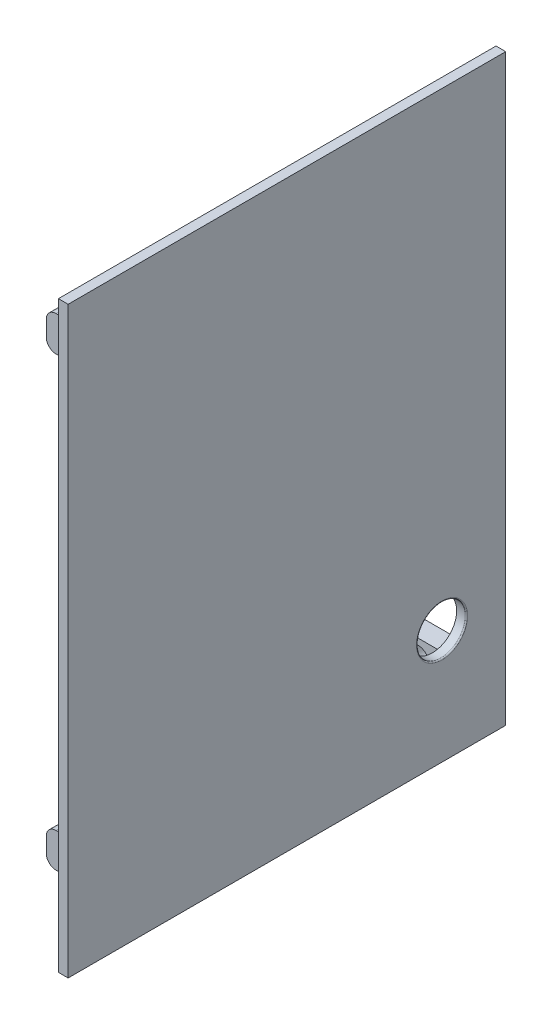
SolidWorks part; units mm, degrees
ref_plane "Front Plane" through (0, 0, 0) normal (0, 0, 1) x (1, 0, 0)
ref_plane "Top Plane" through (0, 0, 0) normal (0, 1, 0) x (1, 0, 0)
ref_plane "Right Plane" through (0, 0, 0) normal (1, 0, 0) x (0, 0, -1)
ref_plane "Plane1" through (282.5307, 0, 0) normal (1, 0, 0) x (0, 0, -1)
sketch "Sketch3" plane through (282.5307, 0, 0) normal (1, 0, 0) x (0, 0, -1)
  line L1 (-31.2372, 19.7391) -> (58.7628, 19.7391)
  line L2 (-31.2372, 19.7391) -> (-31.2372, 139.7391)
  line L3 (-31.2372, 139.7391) -> (58.7628, 139.7391)
  line L4 (58.7628, 19.7391) -> (58.7628, 139.7391)
  point P6 (-32.9944, 79.5028)
extrude "Boss-Extrude1" add sketch "Sketch3" along normal blind 2
sketch "Sketch4" plane through (284.5307, 0, 0) normal (1, 0, 0) x (0, 0, -1)
  circle A0 centre (45.6678, 43.1891) radius 5
  ellipse E0 centre (45.6678, 43.1891) end of major axis (43.4404, 40.9618) minor radius 3.15 construction
  ellipse E1 centre (45.6678, 43.1891) end of major axis (43.4404, 40.9618) minor radius 3.15 construction
  dimension "D1" = 10
extrude "Cut-Extrude1" cut sketch "Sketch4" against normal through all
fillet "Fillet1" radius 0.25 1 edges at (284.5307, 43.1891, -50.6678)
sketch "Sketch5" plane through (282.5307, 0, 0) normal (-1, 0, 0) x (0, 0, 1)
  line L0 (-52.2528, 32.1391) -> (-52.2528, 35.3391) construction
  line L1 (-52.2528, 32.1391) -> (-52.2528, 35.3391)
  line L2 (28.7372, 22.2391) -> (28.7372, 137.2391) construction
  line L3 (-51.7528, 37.2756) -> (-47.7528, 37.2756)
  line L4 (-51.7528, 37.2756) -> (-51.7528, 30.2027)
  line L5 (-51.7528, 30.2027) -> (-47.7528, 30.2027)
  line L6 (-47.7528, 37.2756) -> (-47.7528, 30.2027)
  line L7 (-52.2528, 124.1391) -> (-52.2528, 127.3391) construction
  line L8 (-52.2528, 124.1391) -> (-52.2528, 127.3391)
  line L9 (-56.2628, 137.2391) -> (-56.2628, 22.2391) construction
  line L10 (-52.2528, 122.1391) -> (-48.2528, 122.1391)
  line L11 (-52.2528, 122.1391) -> (-52.2528, 129.3391)
  line L12 (-52.2528, 129.3391) -> (-48.2528, 129.3391)
  line L13 (-48.2528, 122.1391) -> (-48.2528, 129.3391)
  line L14 (23.7372, 30.2027) -> (19.7372, 30.2027)
  line L15 (23.7372, 30.2027) -> (23.7372, 37.2756)
  line L16 (23.7372, 37.2756) -> (19.7372, 37.2756)
  line L17 (19.7372, 30.2027) -> (19.7372, 37.2756)
  line L19 (23.7372, 129.3391) -> (19.7372, 129.3391)
  line L20 (23.7372, 129.3391) -> (23.7372, 122.1391)
  line L21 (23.7372, 122.1391) -> (19.7372, 122.1391)
  line L22 (19.7372, 129.3391) -> (19.7372, 122.1391)
  dimension "D1" = 4
  dimension "D2" = 2
  dimension "D3" = 2
  dimension "D4" = 2
  dimension "D5" = 2
  dimension "D6" = 4
  dimension "D7" = 4.51
  dimension "D8" = 4
  dimension "D9" = 5
  dimension "D10" = 4
  dimension "D11" = 5
extrude "Boss-Extrude2" add sketch "Sketch5" along normal blind 10 contours L10 L13 L12 L11 L8 | L6 L3 L4 L1 L5 | L20 L19 L22 L21 | L15 L14 L17 L16 region at (282.5307, 33.7391, -49.7528) region at (282.5307, 125.7391, -50.2528)
sketch "Sketch6" plane through (0, 0, -48.2528) normal (0, 0, 1) x (1, 0, 0)
  circle A0 centre (277.5307, 33.7391) radius 1.6 construction
  circle A1 centre (277.5307, 125.7391) radius 1.6 construction
  circle A2 centre (277.5307, 33.7391) radius 1.6 construction
  circle A3 centre (277.5307, 125.7391) radius 1.6 construction
  circle A4 centre (277.5307, 33.7391) radius 2.25
  circle A5 centre (277.5307, 125.7391) radius 2.25
  dimension "D1" = 4.5
  dimension "D2" = 4.5
extrude "Cut-Extrude2" cut sketch "Sketch6" against normal through all and the other way through all
fillet "Fillet2" radius 2 8 edges at (272.5307, 129.3391, -50.2528) (272.5307, 122.1391, -50.2528) (272.5307, 129.3391, 21.7372) (272.5307, 122.1391, 21.7372) (272.5307, 37.2756, 21.7372) (272.5307, 30.2027, 21.7372) (272.5307, 37.2756, -49.7528) (272.5307, 30.2027, -49.7528)
equation "\"R_HEATINSERT_BACK\"=4.5"
equation "\"D1@Sketch6\"=\"R_HEATINSERT_BACK\""
equation "\"D2@Sketch6\"=\"R_HEATINSERT_BACK\""
